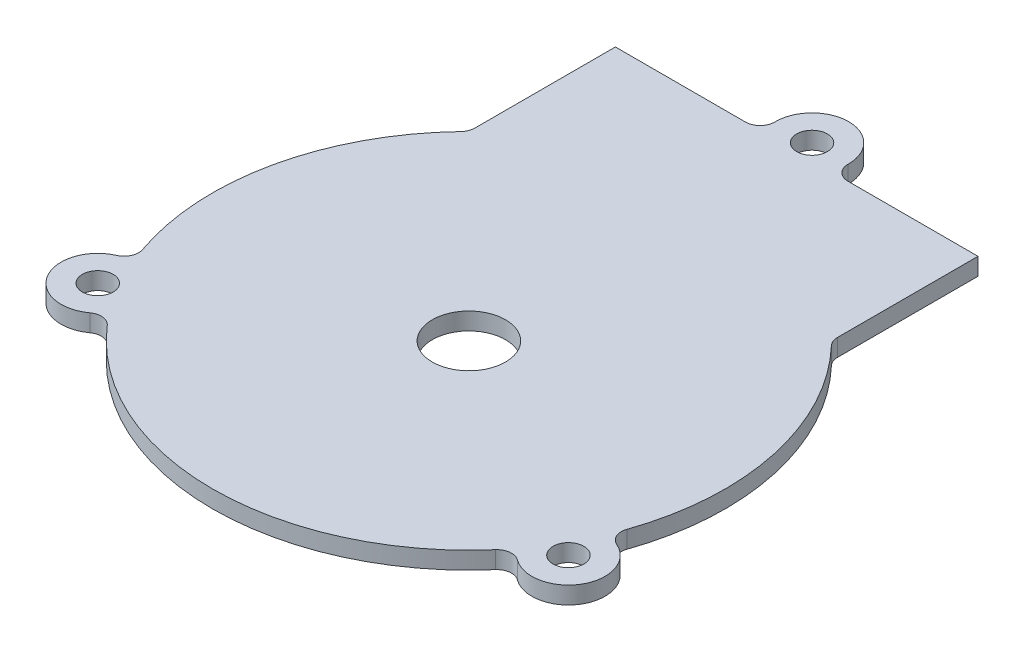
SolidWorks part; units mm, degrees
ref_plane "Front Plane" through (0, 0, 0) normal (0, 0, 1) x (1, 0, 0)
ref_plane "Top Plane" through (0, 0, 0) normal (0, 1, 0) x (1, 0, 0)
ref_plane "Right Plane" through (0, 0, 0) normal (1, 0, 0) x (0, 0, -1)
sketch "Sketch13" plane through (0, 0, 0) normal (0, 1, 0) x (1, 0, 0)
  circle A0 centre (0, 0) radius 35
extrude "Boss-Extrude3" add sketch "Sketch13" along normal blind 2.3622
sketch "Sketch14" plane through (0, 2.3622, 0) normal (0, 1, 0) x (1, 0, 0)
  line L0 (-24.7478, 24.7497) -> (24.7477, 24.7498)
  line L1 (-24.7478, 24.7497) -> (-24.7479, 44.7452)
  line L2 (24.7477, 24.7498) -> (24.7476, 44.7454)
  line L3 (-24.7479, 44.7452) -> (24.7476, 44.7454)
  line L4 (0, 0) -> (60.4611, -34.8658) construction
  line L5 (0, 0) -> (-56.6044, -32.6614) construction
  line L7 (-3.939, 44.1714) -> (-8.8985, 44.1714)
  line L8 (-3.939, 44.1714) -> (-3.939, 47.547)
  line L9 (-3.939, 47.547) -> (-8.8985, 47.547)
  line L10 (-8.8985, 44.1714) -> (-8.8985, 47.547)
  arc A0 (0, 35) -> (-24.7478, 24.7497) centre (0, 0) ccw construction
  circle A1 centre (0, 0) radius 35 construction
  arc A2 (0, 35) -> (-30.3109, -17.4999) centre (0, 0) ccw construction
  arc A3 (0, 35) -> (30.3118, -17.4984) centre (0, 0) ccw
  arc A4 (0, 35) -> (24.7477, 24.7498) centre (0, 0) ccw construction
  circle A5 centre (32.1365, -18.5413) radius 2.1017
  circle A6 centre (32.1365, -18.5413) radius 4.9951
  circle A7 centre (-32.1465, -18.5162) radius 2.0981
  circle A8 centre (-32.1465, -18.5162) radius 4.9995
extrude "Boss-Extrude4" add sketch "Sketch14" against normal up to surface (2.3622 mm away) contours L0 L1 L3 L2 up to face at (0, 0, 35)
sketch "Sketch15" plane through (0, 2.3622, 0) normal (0, 1, 0) x (1, 0, 0)
  line L0 (0, 0) -> (0, 62.3966) construction
  line L1 (-0.0001, 44.7453) -> (0, 46.8414) construction
  line L2 (-24.7479, 44.7452) -> (24.7476, 44.7454) construction
  circle A0 centre (0, 46.8414) radius 2.0961
  circle A1 centre (0, 46.8414) radius 4.996
extrude "Boss-Extrude11" add sketch "Sketch15" against normal up to surface (2.3622 mm away) contours A1 | A0 up to face at (-0.0001, 0, -19.8101)
extrude "Boss-Extrude12" add sketch "Sketch14<6>" against normal up to surface (2.3622 mm away) contours A6 up to face at (0, 0, -29.3038)
sketch "Sketch14<6>" plane through (0, 2.3622, 0) normal (0, 1, 0) x (1, 0, 0) same geometry as "Sketch14"
extrude "Boss-Extrude14" add sketch "Sketch14<8>" against normal up to surface (2.3622 mm away) contours L0 A5 region at (32.1365, 2.3622, 18.5413) up to face at (5.9749, 0, -21.2696)
sketch "Sketch14<8>" plane through (0, 2.3622, 0) normal (0, 1, 0) x (1, 0, 0) same geometry as "Sketch14"
hole_wizard "Ø4.2 (4.2) Diameter Hole1" positions "Sketch22" profile "Sketch23" hole size "Ø4.2" standard "ANSI Metric" end condition through all
sketch "Sketch22" plane through (0, 2.3622, 0) normal (0, 1, 0) x (1, 0, 0)
  point P0 (32.1248, -18.5356)
sketch "Sketch23" plane through (32.1248, 2.3622, 18.5356) normal (1, 0, 0) x (0, 0, 1)
  line L0 (0, 0) -> (0, 2.3622)
  line L1 (0, 2.3622) -> (2.1, 2.3622)
  line L2 (2.1, 2.3622) -> (2.1, 0)
  line L5 (2.1, 0) -> (0, 0)
  line L11 (0, -6.35) -> (0, 107.95) construction
  dimension "Thru Hole Dia." = 4.2
  dimension "Thru Hole Depth" = 2.3622
extrude "Boss-Extrude15" add sketch "Sketch14<11>" against normal up to surface (2.3622 mm away) contours A8 up to face at (32.1248, 0, 20.6356)
sketch "Sketch14<11>" plane through (0, 2.3622, 0) normal (0, 1, 0) x (1, 0, 0) same geometry as "Sketch14"
hole_wizard "Ø4.2 (4.2) Diameter Hole2" positions "Sketch26" profile "Sketch27" hole size "Ø4.2" standard "ANSI Metric" end condition through all
sketch "Sketch26" plane through (0, 2.3622, 0) normal (0, 1, 0) x (1, 0, 0)
  point P0 (-32.148, -18.5088)
  point P2 (-32.148, -18.5088)
sketch "Sketch27" plane through (-32.148, 2.3622, 18.5088) normal (1, 0, 0) x (0, 0, 1)
  line L0 (0, 0) -> (0, 2.3622)
  line L1 (0, 2.3622) -> (2.1, 2.3622)
  line L2 (2.1, 2.3622) -> (2.1, 0)
  line L5 (2.1, 0) -> (0, 0)
  line L11 (0, -6.35) -> (0, 107.95) construction
  dimension "Thru Hole Dia." = 4.2
  dimension "Thru Hole Depth" = 2.3622
fillet "Fillet4" radius 2 1 edges at (-24.7478, 1.1811, -24.7497)
fillet "Fillet6" radius 2 1 edges at (-32.2839, 1.1811, 13.5185)
fillet "Fillet7" radius 2 1 edges at (-27.8924, 1.1811, 21.1427)
fillet "Fillet8" radius 2 1 edges at (27.8812, 1.1811, 21.1574)
fillet "Fillet9" radius 2 1 edges at (32.2715, 1.1811, 13.548)
fillet "Fillet10" radius 2 1 edges at (24.7477, 1.1811, -24.7498)
fillet "Fillet11" radius 2 1 edges at (4.535, 1.1811, -44.7453)
fillet "Fillet12" radius 2 1 edges at (-4.535, 1.1811, -44.7453)
sketch "Sketch28" plane through (0, 2.3622, 0) normal (0, 1, 0) x (1, 0, 0)
  circle A0 centre (0, 0) radius 5
extrude "Cut-Extrude1" cut sketch "Sketch28" against normal up to surface (2.3622 mm away) up to face at (-32.148, 0, 20.6088)
